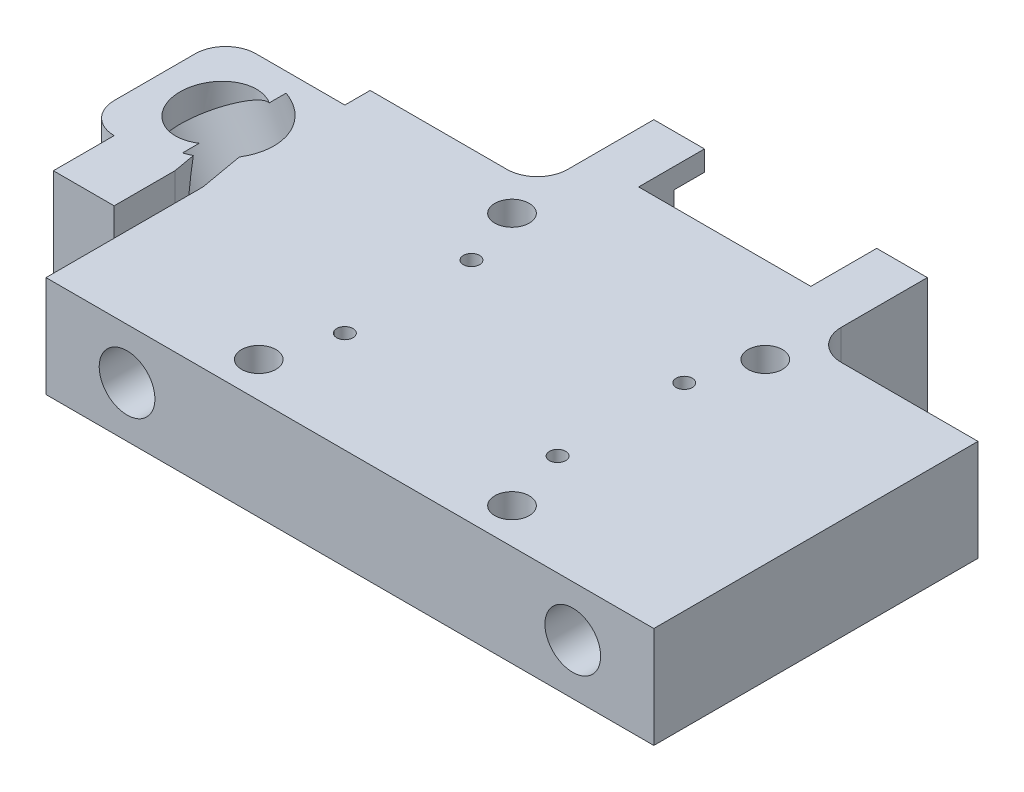
SolidWorks part; units mm, degrees
ref_plane "Front Plane" through (0, 0, 0) normal (0, 0, 1) x (1, 0, 0)
ref_plane "Top Plane" through (0, 0, 0) normal (0, 1, 0) x (1, 0, 0)
ref_plane "Right Plane" through (0, 0, 0) normal (1, 0, 0) x (0, 0, -1)
sketch "Sketch1" plane through (0, 0, 0) normal (0, 1, 0) x (1, 0, 0)
  line L1 (-12.5, 12.5) -> (12.5, 12.5)
  line L2 (-12.5, 12.5) -> (-12.5, -12.5)
  line L3 (-12.5, -12.5) -> (12.5, -12.5)
  line L4 (12.5, 12.5) -> (12.5, -12.5)
  line L5 (-12.5, 12.5) -> (12.5, -12.5) construction
  line L6 (-12.5, -12.5) -> (12.5, 12.5) construction
  line L7 (-30, 16) -> (30, 16)
  line L8 (-30, 16) -> (-30, -16)
  line L9 (-30, -16) -> (30, -16)
  line L10 (30, 16) -> (30, -16)
  line L11 (-30, 16) -> (30, -16) construction
  line L12 (-30, -16) -> (30, 16) construction
  point P0 (0, 0)
  point P6 (0, 0)
  dimension "D1" = 25
  dimension "D2" = 32
  dimension "D3" = 60
sketch "Sketch2" plane through (0, 0, 0) normal (0, 1, 0) x (1, 0, 0)
  line L0 (-30, 16) -> (30, 16) construction
  line L1 (30, 16) -> (30, -16) construction
  line L2 (-30, -16) -> (30, -16) construction
  line L3 (-30, 16) -> (-30, -16) construction
  line L4 (-30, 16) -> (30, 16)
  line L5 (30, 16) -> (30, -16)
  line L6 (-30, -16) -> (30, -16)
  line L7 (-30, 16) -> (-30, -16)
extrude "Boss-Extrude1" add sketch "Sketch2" along normal blind 10
hole_wizard "CBORE for M3 SHCS1" positions "Sketch3" profile "Sketch4" counterbore size "M3" standard "ANSI Metric" end condition through all
sketch "Sketch3" plane through (0, 0, 0) normal (0, -1, 0) x (-1, 0, 0)
  point P0 (12.5, 12.5)
  point P2 (12.5, -12.5)
  point P5 (-12.5, -12.5)
  point P8 (-12.5, 12.5)
sketch "Sketch4" plane through (-12.5, 0, -12.5) normal (1, 0, 0) x (0, 0, -1)
  line L0 (0, 0) -> (0, 10)
  line L1 (0, 10) -> (1.7, 10)
  line L3 (1.7, 10) -> (1.7, 5)
  line L4 (1.7, 5) -> (3.25, 5)
  line L5 (3.25, 5) -> (3.25, 0)
  line L7 (3.25, 0) -> (0, 0)
  line L11 (0, -6.35) -> (0, 107.95) construction
  dimension "Thru Hole Dia." = 3.4
  dimension "Thru Hole Depth" = 10
  dimension "C'Bore Dia." = 6.5
  dimension "C'Bore Depth" = 5
sketch "Sketch6" plane through (0, 0, 0) normal (0, -1, 0) x (-1, 0, 0)
  line L1 (8.5, 4) -> (-8.5, 4)
  line L2 (8.5, 4) -> (8.5, 16)
  line L3 (8.5, 16) -> (-8.5, 16)
  line L4 (-8.5, 4) -> (-8.5, 16)
  line L5 (30, 16) -> (-30, 16) construction
  line L6 (0, 0) -> (0, 4) construction
  dimension "D1" = 17
  dimension "D2" = 12
extrude "Cut-Extrude2" cut sketch "Sketch6" against normal blind 2
sketch "Sketch8" plane through (0, 0, -16) normal (0, 0, -1) x (-1, 0, 0)
  line L0 (30, 5) -> (-30, 5) construction
  line L1 (30, 10) -> (30, 0) construction
  line L2 (-30, 10) -> (-30, 0) construction
  line L4 (17.2657, 5) -> (19.6329, 0.9)
  line L5 (19.6329, 0.9) -> (24.3671, 0.9)
  line L6 (24.3671, 0.9) -> (26.7343, 5)
  line L7 (26.7343, 5) -> (24.3671, 9.1)
  line L8 (24.3671, 9.1) -> (19.6329, 9.1)
  line L9 (19.6329, 9.1) -> (17.2657, 5)
  line L10 (-17.2657, 5) -> (-19.6329, 9.1)
  line L11 (-19.6329, 9.1) -> (-24.3671, 9.1)
  line L12 (-24.3671, 9.1) -> (-26.7343, 5)
  line L13 (-26.7343, 5) -> (-24.3671, 0.9)
  line L14 (-24.3671, 0.9) -> (-19.6329, 0.9)
  line L15 (-19.6329, 0.9) -> (-17.2657, 5)
  circle A0 centre (22, 5) radius 4.1 construction
  circle A1 centre (-22, 5) radius 4.1 construction
  dimension "D1" = 8.2
  dimension "D2" = 8
  dimension "D3" = 8
extrude "Cut-Extrude4" cut sketch "Sketch8" against normal blind 5
hole_wizard "M5 Clearance Hole1" positions "Sketch10" profile "Sketch11" hole size "M5" standard "ANSI Metric" end condition through all
sketch "Sketch10" plane through (0, 0, -11) normal (0, 0, -1) x (-1, 0, 0)
  line L0 (19.6329, 0.9) -> (24.3671, 9.1)
  line L2 (-19.6329, 9.1) -> (-24.3671, 0.9)
  point P0 (22, 5)
  point P2 (-22, 5)
sketch "Sketch11" plane through (-22, 5, -11) normal (1, 0, 0) x (0, 1, 0)
  line L0 (0, 0) -> (0, 27)
  line L1 (0, 27) -> (2.75, 27)
  line L2 (2.75, 27) -> (2.75, 0)
  line L5 (2.75, 0) -> (0, 0)
  line L11 (0, -6.35) -> (0, 107.95) construction
  dimension "Thru Hole Dia." = 5.5
  dimension "Thru Hole Depth" = 27
sketch "Sketch12" plane through (0, 0, 0) normal (0, -1, 0) x (1, 0, 0)
  line L0 (-8.5, -16) -> (-30, -16) construction
  line L1 (12.5, -16) -> (-12.5, -16) construction
  line L2 (12.5, -16) -> (12.5, 8) construction
  line L3 (12.5, 8) -> (-12.5, 8) construction
  line L4 (-12.5, -16) -> (-12.5, 8) construction
  line L7 (10.5, -6.5) -> (-10.5, -6.5) construction
  line L8 (10.5, -6.5) -> (10.5, 6) construction
  line L9 (10.5, 6) -> (-10.5, 6) construction
  line L10 (-10.5, -6.5) -> (-10.5, 6) construction
  line L11 (10.5, -6.5) -> (-10.5, 6) construction
  line L12 (10.5, 6) -> (-10.5, -6.5) construction
  circle A0 centre (10.5, -6.5) radius 2
  circle A1 centre (-10.5, -6.5) radius 2
  circle A2 centre (10.5, 6) radius 2
  circle A3 centre (-10.5, 6) radius 2
  point P6 (0, -0.25)
  dimension "D1" = 24
  dimension "D2" = 25
  dimension "D3" = 2
  dimension "D4" = 12.5
  dimension "D5" = 21
extrude "Boss-Extrude2" add sketch "Sketch12" along normal blind 2.5
hole_wizard "M2x0.4 Tapped Hole1" positions "Sketch13" profile "Sketch14" tap size "M2x0.4" standard "ANSI Metric" end condition through all
sketch "Sketch13" plane through (0, -2.5, 0) normal (0, -1, 0) x (-1, 0, 0)
  circle A0 centre (10.5, 6.5) radius 2 construction
  circle A1 centre (-10.5, -6) radius 2 construction
  point P0 (-10.5, -6)
  point P2 (-10.5, 6.5)
  point P5 (10.5, -6)
  point P8 (10.5, 6.5)
sketch "Sketch14" plane through (10.5, -2.5, 6) normal (1, 0, 0) x (0, 0, -1)
  line L0 (0, 0) -> (0, 12.5)
  line L1 (0, 12.5) -> (0.8, 12.5)
  line L2 (0.8, 12.5) -> (0.8, 0)
  line L5 (0.8, 0) -> (0, 0)
  line L11 (0, -6.35) -> (0, 107.95) construction
  dimension "Thru Tap Drill Dia." = 1.6
  dimension "Thru Tap Drill Depth" = 12.5
cosmetic thread "Hole Thread1" parameters "D2"=2
cosmetic thread "Hole Thread2" parameters "D2"=2
cosmetic thread "Hole Thread3" parameters "D2"=2
cosmetic thread "Hole Thread4" parameters "D2"=2
sketch "Sketch15" plane through (0, 0, -16) normal (0, 0, -1) x (-1, 0, 0)
  line L0 (-13.5, 0) -> (-13.5, 10)
  line L1 (13.5, 0) -> (13.5, 10)
  line L8 (-8.5, 2) -> (8.5, 2)
  line L9 (8.5, 2) -> (8.5, 0)
  line L10 (8.5, 0) -> (30, 0)
  line L11 (30, 0) -> (30, 10)
  line L12 (30, 10) -> (-30, 10)
  line L13 (-30, 10) -> (-30, 0)
  line L14 (-30, 0) -> (-8.5, 0)
  line L15 (-8.5, 0) -> (-8.5, 2)
  line L16 (-8.5, 2) -> (8.5, 2)
  line L17 (8.5, 2) -> (8.5, 0)
  line L18 (8.5, 0) -> (13.5, 0)
  line L20 (13.5, 10) -> (-13.5, 10)
  line L22 (-13.5, 0) -> (-8.5, 0)
  line L23 (-8.5, 0) -> (-8.5, 2)
  dimension "D2" = 5
  dimension "D3" = 5
  dimension "D4" = 27
  dimension "D1" = 0
extrude "Boss-Extrude3" add sketch "Sketch15" along normal blind 5
sketch "Sketch16" plane through (0, 0, -21) normal (0, 0, -1) x (-1, 0, 0)
  line L0 (0, 0) -> (0, 10) construction
  line L1 (13.5, 10) -> (-13.5, 10) construction
  line L2 (-10.75, 8) -> (10.75, 8)
  line L3 (0, 0) -> (0, -4.7) construction
  line L4 (10.75, -4.7) -> (-10.75, -4.7)
  point P8 (0, 8)
  point P11 (0, -4.7)
  point P12 (0, 0)
  point P13 (0, 0)
  point P14 (0, 0)
  point P15 (0, 0)
  dimension "D1" = 21.5
  dimension "D2" = 2
  dimension "D3" = 12.7
sketch "Sketch19" plane through (0, 0, -21) normal (0, 0, -1) x (-1, 0, 0)
  line L0 (13.5, 0) -> (13.5, -6.7)
  line L9 (-8.5, 0) -> (-13.5, 0) construction
  line L10 (-8.5, 0) -> (-8.5, 10)
  line L11 (-8.5, 10) -> (-13.5, 10)
  line L12 (-13.5, 0) -> (-13.5, 10)
  line L13 (8.5, 0) -> (13.5, 0) construction
  line L14 (8.5, 0) -> (8.5, 10)
  line L15 (8.5, 10) -> (13.5, 10)
  line L16 (13.5, 0) -> (13.5, 10)
  line L17 (13.5, -6.7) -> (8.5, -6.7)
  line L18 (8.5, -6.7) -> (8.5, 0)
  line L19 (-8.5, 0) -> (-8.5, -6.7)
  line L20 (-8.5, -6.7) -> (-13.5, -6.7)
  line L21 (-13.5, -6.7) -> (-13.5, 0)
  line L23 (10.75, -4.7) -> (-10.75, -4.7) construction
  dimension "D1" = 2
extrude "Boss-Extrude4" add sketch "Sketch19" along normal blind 6.5
fillet "Fillet1" radius 4 2 edges at (11, 0, -21) (-11, 0, -21)
hole_wizard "M2x0.4 Tapped Hole2" positions "Sketch20" profile "Sketch22" tap size "M2x0.4" standard "ANSI Metric"
sketch "Sketch20" plane through (0, 0, -27.5) normal (0, 0, -1) x (-1, 0, 0)
  point P0 (10.75, -4.7)
  point P2 (-10.75, -4.7)
  point P4 (-10.75, 8)
  point P6 (10.75, 8)
  point P10 (0, 0)
  point P11 (0, 0)
  point P14 (0, 0)
  point P16 (0, 0)
sketch "Sketch22" plane through (-10.75, -4.7, -27.5) normal (1, 0, 0) x (0, 1, 0)
  line L0 (0, 0) -> (0, 5.6807)
  line L1 (0, 5.6807) -> (0.8, 5.2)
  line L2 (0.8, 5.2) -> (0.8, 0)
  line L5 (0.8, 0) -> (0, 0)
  line L10 (0, 5.6807) -> (-0.8, 5.2) construction
  line L11 (0, -6.35) -> (0, 107.95) construction
  dimension "Tap Drill Dia." = 1.6
  dimension "Tap Drill Depth" = 5.2
  dimension "Drill Angle" = 118
sketch "Sketch23" plane through (0, 0, -27.5) normal (0, 0, -1) x (-1, 0, 0)
  line L0 (8.5, 8) -> (11.5, 5)
  line L1 (8.5, 10) -> (8.5, -6.7) construction
  line L2 (11.5, 5) -> (11.5, -1.7)
  line L3 (11.5, -1.7) -> (8.5, -4.7)
  line L4 (8.5, -4.7) -> (-8.5, -4.7)
  line L5 (-8.5, -6.7) -> (-8.5, 10) construction
  line L6 (-8.5, -4.7) -> (-11.5, -1.7)
  line L7 (-11.5, -1.7) -> (-11.5, 5)
  line L8 (-11.5, 5) -> (-8.5, 8)
  line L9 (8.5, 8) -> (-8.5, 8)
  line L10 (13.5, 10) -> (8.5, 10) construction
  line L11 (8.5, -6.7) -> (13.5, -6.7) construction
  line L12 (13.5, -6.7) -> (13.5, 10) construction
  line L13 (-13.5, 10) -> (-13.5, -6.7) construction
  point P5 (8.5, -4.8565)
  dimension "D1" = 45
  dimension "D2" = 2
  dimension "D3" = 2
  dimension "D4" = 2
  dimension "D5" = 2
extrude "Cut-Extrude5" cut sketch "Sketch23" against normal blind 3
chamfer "Chamfer1" distance 1 angle 45 4 edges at (10.5, 0, -8.5) (10.5, 0, 8) (-10.5, 0, 8) (-10.5, 0, -8.5)
sketch "Sketch24" plane through (0, 0, 16) normal (0, 0, 1) x (1, 0, 0)
  line L0 (0, 0) -> (0, -60) construction
  line L1 (-30, 0) -> (30, 0) construction
  line L2 (0, -60) -> (-29.2825, -3.3632) construction
  line L3 (-29.2825, -3.3632) -> (0, 0) construction
  line L4 (-39.7713, 4.948) -> (-34.1682, -5.8892)
  line L5 (-39.7713, 4.948) -> (-30, 10)
  line L6 (-34.1682, -5.8892) -> (-24.3969, -0.8372)
  line L7 (-30, 10) -> (-24.3969, -0.8372)
  line L8 (-39.7713, 4.948) -> (-24.3969, -0.8372) construction
  line L9 (-34.1682, -5.8892) -> (-30, 10) construction
  line L10 (-30, 10) -> (30, 10) construction
  point P4 (0, 0)
  point P6 (-32.0841, 2.0554)
  point P7 (0, -29.9447)
  point P12 (-31.2947, 5.0627)
  point P13 (-32.1017, 5.0026)
  point P14 (0, 0)
  point P17 (-30.5508, 1.8887)
  point P18 (0, 0)
  point P19 (0, 0)
  point P20 (0, 0)
  point P21 (0, 0)
  dimension "D1" = 60
  dimension "D2" = 11
  dimension "D3" = 12.2
  dimension "D4" = 30
sketch "Sketch25" plane through (0, 0, 0) normal (0, -1, 0) x (1, 0, 0)
  line L0 (-10.5, -6.5) -> (-30, -6.5) construction
  line L1 (-30, -16) -> (-30, 16) construction
  line L2 (-30, 0.5) -> (-30, -6.5)
  line L3 (-30, -13.5) -> (-41.7713, -13.5)
  line L4 (-18.2287, -13.5) -> (-18.2287, 0.5) construction
  line L5 (-30, 0.5) -> (-41.7713, 0.5)
  line L6 (-41.7713, -13.5) -> (-41.7713, 0.5)
  line L7 (-18.2287, -13.5) -> (-41.7713, 0.5) construction
  line L8 (-18.2287, 0.5) -> (-41.7713, -13.5) construction
  line L9 (-30, -6.5) -> (-30, -13.5)
  point P9 (-39.7713, 16)
  point P12 (-41.1443, -12.9883)
  dimension "D1" = 2
  dimension "D2" = 14
extrude "Boss-Extrude5" add sketch "Sketch25" against normal up to surface (10 mm away) up to face at (10.5, 10, 5.2)
ref_plane "Plane1" through (-34.1682, -5.8892, 16) normal (0.4593, -0.8883, 0) x (-0.8883, -0.4593, 0)
sketch "Sketch26" plane through (-34.1682, -5.8892, 16) normal (0.4593, -0.8883, 0) x (-0.8883, -0.4593, 0)
  line L0 (-22.5809, 22.5) -> (-5.5, 22.5) construction
  line L1 (-5.5, 0) -> (-5.5, 22.5) construction
  circle A0 centre (-5.5, 22.5) radius 5.5
  ellipse E1 centre (-22.5809, 22.5) end of major axis (-22.5809, 21.7) minor radius 0.7106 construction
  point P3 (0, 0)
  point P9 (-5.5, 22.5164)
  point P14 (0, 0)
  dimension "D1" = 11
extrude "Cut-Extrude7" cut sketch "Sketch26" against normal blind 14
sketch "Sketch27" plane through (-11.2342, 21.7287, 0) normal (0.4593, -0.8883, 0) x (0.8883, 0.4593, 0)
  line L1 (-25.5377, -11.6162) -> (-25.5377, -1.3838)
  line L2 (-25.5377, -11.6162) -> (-25.5377, -1.3838) construction
  circle A0 centre (-27.5562, -6.5) radius 4
  arc A1 (-25.5377, -1.3838) -> (-25.5377, -11.6162) centre (-27.5562, -6.5) ccw
  arc A2 (-25.5377, -1.3838) -> (-25.5377, -11.6162) centre (-27.5562, -6.5) ccw construction
  dimension "D2" = 8
  dimension "D1" = 0
extrude "Cut-Extrude8" cut sketch "Sketch27" along direction (0, -1, 0) on the side against the normal blind 14
fillet "Fillet2" radius 3 4 edges at (-13.5, 5, -16) (13.5, 5, -16) (-41.7713, 5, 0.5) (-41.7713, 5, -13.5)
sketch "Sketch28" plane through (0, 0, 0) normal (0, -1, 0) x (1, 0, 0)
  line L1 (-38.7713, 0.5) -> (-32.7713, 0.5)
  line L2 (-38.7713, 0.5) -> (-38.7713, 6.5)
  line L3 (-38.7713, 6.5) -> (-32.7713, 6.5)
  line L4 (-32.7713, 0.5) -> (-32.7713, 6.5)
  dimension "D1" = 6
  dimension "D2" = 6
extrude "Boss-Extrude6" add sketch "Sketch28" against normal up to surface (10 mm away) up to face at (-34.2752, 10, -6.4586)
sketch "Sketch29" plane through (0, 0, 0) normal (0, -1, 0) x (1, 0, 0)
  line L0 (-30, 0.5) -> (-31.1255, -5.8828)
  line L1 (-31.1255, -5.8828) -> (-33.8132, -5.4088)
  line L2 (-33.8132, -5.4088) -> (-32.7713, 0.5)
  line L3 (-32.7713, 0.5) -> (-30, 0.5)
  dimension "D1" = 100
  dimension "D2" = 6
extrude "Cut-Extrude9" cut sketch "Sketch29" against normal through all
sketch "Sketch30" plane through (-38.7713, 0, 0) normal (-1, 0, 0) x (0, 0, 1)
  line L0 (3.5, 0) -> (3.5, 10) construction
  line L1 (6.5, 0) -> (0.5, 0) construction
  line L2 (6.5, 10) -> (0.5, 10) construction
  circle A0 centre (3.5, 5) radius 1.6
  dimension "D1" = 3.2
extrude "Cut-Extrude10" cut sketch "Sketch30" against normal up to next
sketch "Sketch31" plane through (-30, 0, 0) normal (-1, 0, 0) x (0, 0, 1)
  circle A0 centre (3.5, 5) radius 1.6 construction
  circle A1 centre (3.5, 5) radius 1.6 construction
  circle A2 centre (3.5, 5) radius 1.4
  dimension "D1" = 2.8
extrude "Cut-Extrude11" cut sketch "Sketch31" against normal blind 5
